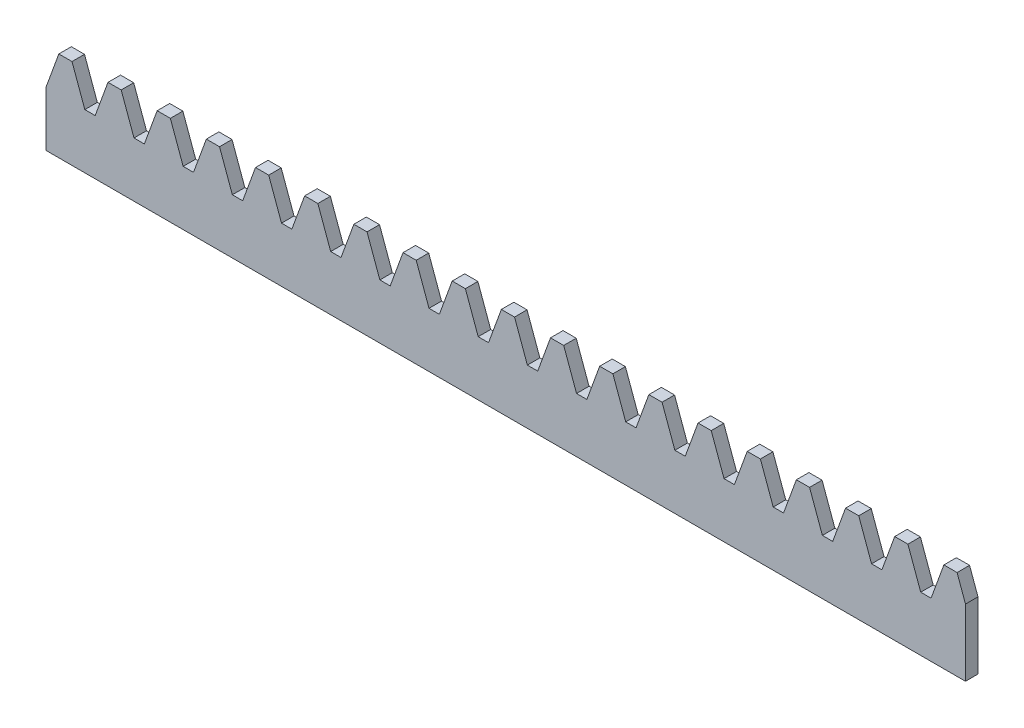
SolidWorks part; units mm, degrees
ref_plane "前视基准面" through (0, 0, 0) normal (0, 0, 1) x (1, 0, 0)
ref_plane "上视基准面" through (0, 0, 0) normal (0, 1, 0) x (1, 0, 0)
ref_plane "右视基准面" through (0, 0, 0) normal (1, 0, 0) x (0, 0, -1)
sketch "草图1" plane through (0, 0, 0) normal (0, 0, 1) x (1, 0, 0)
  line L1 (0, 0) -> (94.2478, 0)
  line L2 (0, 0) -> (0, -10)
  line L3 (0, -10) -> (94.2478, -10)
  line L4 (94.2478, 0) -> (94.2478, -10)
  dimension "D1" = 10
  dimension "L" = 94.2478
extrude "拉伸1" add sketch "草图1" along normal blind 30
sketch "草图2" plane through (0, 0, 30) normal (0, 0, 1) x (1, 0, 0)
  line L0 (0, 0) -> (0.8189, 2.25)
  line L1 (0.8189, 2.25) -> (1.6618, 2.25)
  line L2 (1.6618, 2.25) -> (2.4807, 0)
  line L3 (94.2478, 0) -> (0, 0) construction
  line L4 (0, 0) -> (2.4807, 0)
  line L5 (0.455, 1.25) -> (2.0258, 1.25) construction
  dimension "D2" = 70
  dimension "alpha" = 110
  dimension "ha" = 1
  dimension "hf" = 1.25
  dimension "S" = 1.5708
extrude "拉伸2" add sketch "草图2" against normal up to surface (30 mm away) up to face at (47.1239, -5, 0)
pattern_linear "阵列(线性)1" count 30 spacing 3.1416 along (1, 0, 0) of "拉伸2"
sketch "草图3" plane through (0, 0, 30) normal (0, 0, 1) x (1, 0, 0)
  line L1 (-12.0886, 17.554) -> (115.6309, 17.554)
  line L2 (-12.0886, 17.554) -> (-12.0886, -30.2189)
  line L3 (-12.0886, -30.2189) -> (115.6309, -30.2189)
  line L4 (115.6309, 17.554) -> (115.6309, -30.2189)
extrude "切除-拉伸1" cut sketch "草图3" against normal blind 29.2
sketch "草图4" plane through (0, -10, 0) normal (0, -1, 0) x (1, 0, 0)
  line L1 (-7.7337, 19.6292) -> (109.1312, 19.6292)
  line L2 (-7.7337, 19.6292) -> (-7.7337, -21.7741)
  line L3 (-7.7337, -21.7741) -> (109.1312, -21.7741)
  line L4 (109.1312, 19.6292) -> (109.1312, -21.7741)
extrude "切除-拉伸2" cut sketch "草图4" against normal blind 6.5
sketch "草图5" plane through (94.2478, 0, 0) normal (1, 0, 0) x (0, 0, -1)
  line L1 (-4.0313, 2.415) -> (3.7656, 2.415)
  line L2 (-4.0313, 2.415) -> (-4.0313, -5.7325)
  line L3 (-4.0313, -5.7325) -> (3.7656, -5.7325)
  line L4 (3.7656, 2.415) -> (3.7656, -5.7325)
extrude "切除-拉伸3" cut sketch "草图5" against normal blind 35.5
equation "\"d\"=\"S@草图2\" * 2"
equation "\"z\"= int(  \"L@草图1\" / (  \"S@草图2\" * 2 ) + 0.5 )"
